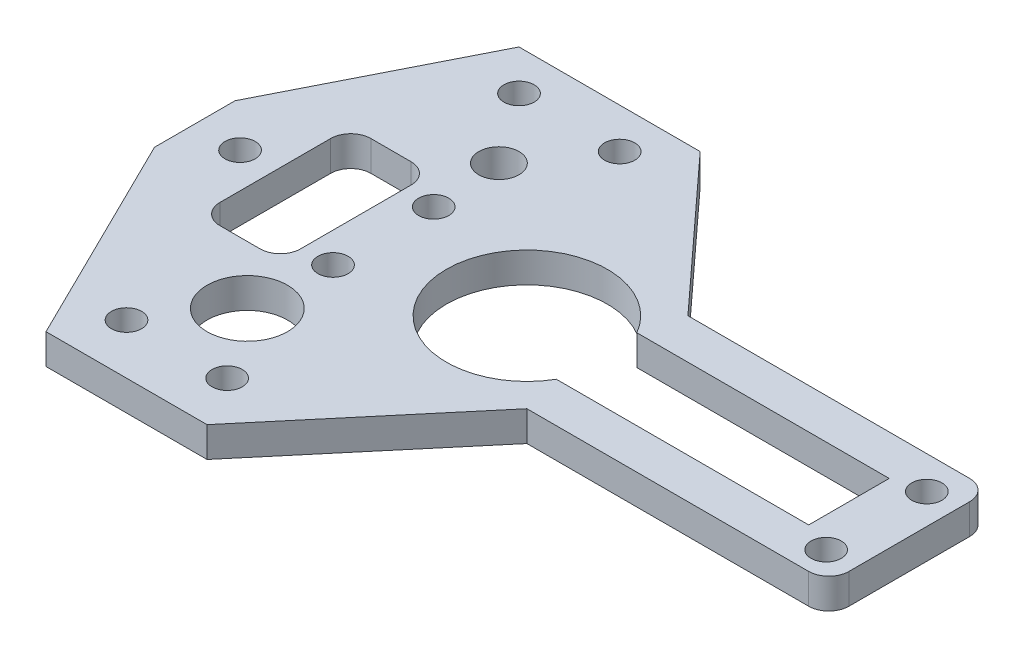
SolidWorks part; units mm, degrees
ref_plane "Piano frontale" through (0, 0, 0) normal (0, 0, 1) x (1, 0, 0)
ref_plane "Piano superiore" through (0, 0, 0) normal (0, 1, 0) x (1, 0, 0)
ref_plane "Piano destro" through (0, 0, 0) normal (1, 0, 0) x (0, 0, -1)
sketch "Sketch1" plane through (0, 0, 0) normal (0, 1, 0) x (1, 0, 0)
  line L0 (-18.4803, -4) -> (-18.4803, 4)
  line L1 (-18.4803, 4) -> (-9, 22.7383)
  line L2 (-9, 22.7383) -> (9, 22.7383)
  line L3 (9, 22.7383) -> (22.5197, 8)
  line L4 (22.5197, 8) -> (52.5197, 8)
  line L5 (52.5197, 8) -> (52.5197, -8)
  line L6 (52.5197, -8) -> (22.5197, -8)
  line L7 (22.5197, -8) -> (8, -25.2617)
  line L8 (8, -25.2617) -> (-8, -25.2617)
  line L9 (-8, -25.2617) -> (-18.4803, -4)
  line L10 (-18.4803, 0) -> (52.5197, 0) construction
  line L11 (0, -25.2617) -> (0, 22.7383) construction
  dimension "D1" = 8
  dimension "D2" = 18
  dimension "D3" = 16
  dimension "D4" = 21
  dimension "D5" = 48
  dimension "D6" = 16
  dimension "D7" = 30
  dimension "D8" = 20
  dimension "D9" = 71
base flange "Base-Flange1" sketch "Sketch1" thickness 3 reverse thickness direction yes parameters "D1"=0.7366
sketch "Sketch2" plane through (0, 3, 0) normal (0, 1, 0) x (1, 0, 0)
  line L0 (-18.4803, 0) -> (52.5197, 0) construction
  line L1 (52.5197, -8) -> (52.5197, 8) construction
  line L3 (21.4479, 4) -> (46.5197, 4)
  line L5 (21.4479, -4) -> (46.5197, -4)
  line L6 (46.5197, 4) -> (46.5197, -4)
  arc A0 (21.4479, 4) -> (21.4479, -4) centre (14.5197, 0) ccw
  point P10 (46.5197, 0)
  dimension "D1" = 16
  dimension "D2" = 38
  dimension "D3" = 8
  dimension "D4" = 6
extrude "Cut-Extrude1" cut sketch "Sketch2" against normal up to next normal cut yes
sketch "Sketch3" plane through (0, 3, 0) normal (0, 1, 0) x (1, 0, 0)
  line L0 (-18.4803, 0) -> (52.5197, 0) construction
  line L1 (-10.4803, -7.5) -> (-2.4803, -7.5)
  line L2 (-10.4803, -7.5) -> (-10.4803, 7.5)
  line L3 (-10.4803, 7.5) -> (-2.4803, 7.5)
  line L4 (-2.4803, -7.5) -> (-2.4803, 7.5)
  line L5 (-10.4803, -7.5) -> (-2.4803, 7.5) construction
  line L6 (-10.4803, 7.5) -> (-2.4803, -7.5) construction
  line L7 (-18.4803, 4) -> (-18.4803, -4) construction
  circle A0 centre (-13.9803, 0) radius 1.5
  arc A1 (21.4479, 4) -> (21.4479, -4) centre (14.5197, 0) ccw construction
  point P0 (-6.4803, 0)
  dimension "D1" = 3
  dimension "D2" = 8
  dimension "D3" = 15
  dimension "D4" = 17
  dimension "D5" = 4.5
extrude "Cut-Extrude2" cut sketch "Sketch3" against normal up to next normal cut yes
sketch "Sketch4" plane through (0, 3, 0) normal (0, 1, 0) x (1, 0, 0)
  line L0 (9, 22.7383) -> (-9, 22.7383) construction
  line L1 (-18.4803, 4) -> (-18.4803, -4) construction
  circle A0 centre (-5, 18.7383) radius 1.5
  circle A1 centre (5, 18.7383) radius 1.5
  circle A2 centre (0.5197, 4.7383) radius 1.5
  circle A3 centre (-5, -20.2617) radius 1.5
  circle A4 centre (5, -20.2617) radius 1.5
  circle A5 centre (0.5197, -5.2617) radius 1.5
  circle A6 centre (49.5197, 4.7383) radius 1.5
  circle A7 centre (49.5197, -5.2617) radius 1.5
  point P11 (0, 22.7383)
  dimension "D1" = 10
  dimension "D2" = 3
  dimension "D5" = 18
  dimension "D3" = 5
  dimension "D4" = 4
  dimension "D6" = 19
  dimension "D7" = 39
  dimension "D8" = 10
  dimension "D9" = 49
extrude "Cut-Extrude3" cut sketch "Sketch4" against normal up to next normal cut yes
sketch "Sketch5" plane through (0, 3, 0) normal (0, 1, 0) x (1, 0, 0)
  line L0 (0, -25.2617) -> (0, 22.7383) construction
  line L1 (-8, -25.2617) -> (8, -25.2617) construction
  line L2 (9, 22.7383) -> (-9, 22.7383) construction
  circle A0 centre (0, 11.7383) radius 2
  circle A1 centre (0, -13.2617) radius 4
  dimension "D1" = 8
  dimension "D4" = 4
  dimension "D2" = 12
  dimension "D3" = 11
extrude "Cut-Extrude4" cut sketch "Sketch5" against normal up to next normal cut yes
fillet "Fillet1" radius 2 6 edges at (-2.4803, 1.5, 7.5) (-10.4803, 1.5, 7.5) (-2.4803, 1.5, -7.5) (-10.4803, 1.5, -7.5) (52.5197, 1.5, 8) (52.5197, 1.5, -8)
sketch "Linee di piegatura1" [suppressed] plane through (0, 0, 0) normal (0, 1, 0) x (1, 0, 0)
sketch "Casella di contorno1" [suppressed] plane through (0, 0, 0) normal (0, 1, 0) x (1, 0, 0)
sheet metal parameters "Lamiera1" thickness 3 parameters "D1"=0.7366
flat pattern "Ripetizione piatta1" [suppressed]
sketch "Linee di piegatura2" plane through (0, 0, 0) normal (0, 1, 0) x (1, 0, 0)
sketch3d "Casella di contorno2" [suppressed]
  line L0 (-53.2984, 24, 0) -> (17.7016, 24, 0) construction
  line L1 (-53.2984, -24, 0) -> (17.7016, -24, 0) construction
  line L2 (-53.2984, 24, 0) -> (-53.2984, -24, 0) construction
  line L3 (17.7016, 24, 0) -> (17.7016, -24, 0) construction
sheet metal parameters "Lamiera2" thickness 3 parameters "D1"=0.7366
flat pattern "Ripetizione piatta1" [suppressed]
sketch "Linee di piegatura2" plane through (0, 0, 0) normal (0, 1, 0) x (1, 0, 0)
sketch3d "Casella di contorno2" [suppressed]
  line L0 (-51, -24, 0) -> (20, -24, 0) construction
  line L1 (-51, 24, 0) -> (20, 24, 0) construction
  line L2 (-51, -24, 0) -> (-51, 24, 0) construction
  line L3 (20, -24, 0) -> (20, 24, 0) construction
sketch "Sketch10-2" [suppressed] plane through (0, 3, 0) normal (0, 1, 0) x (1, 0, 0)
  line L1 (-9, -24) -> (9, -24) construction
  circle A0 centre (0.5197, 10.4281) radius 2
  circle A1 centre (0, -12) radius 4
  dimension "D1" = 4
  dimension "D2" = 8
  dimension "D3" = 12
sheet metal parameters "Lamiera3" thickness 3 parameters "D1"=0.7366
flat pattern "Ripetizione piatta1" [suppressed]
sketch "Linee di piegatura2" plane through (0, 0, 0) normal (0, 1, 0) x (1, 0, 0)
sketch3d "Casella di contorno2" [suppressed]
  line L0 (-51, -24, 0) -> (20, -24, 0) construction
  line L1 (-51, 24, 0) -> (20, 24, 0) construction
  line L2 (-51, -24, 0) -> (-51, 24, 0) construction
  line L3 (20, -24, 0) -> (20, 24, 0) construction
sketch "Sketch10-3" [suppressed] plane through (0, 3, 0) normal (0, 1, 0) x (1, 0, 0)
  line L1 (-9, -24) -> (9, -24) construction
  circle A0 centre (0.5197, 10.4281) radius 2
  circle A1 centre (0, -12) radius 4
  dimension "D1" = 4
  dimension "D2" = 8
  dimension "D3" = 12
sheet metal parameters "Lamiera4" thickness 3 parameters "D1"=0.7366
flat pattern "Ripetizione piatta1" [suppressed]
sketch "Linee di piegatura2" plane through (0, 0, 0) normal (0, 1, 0) x (1, 0, 0)
sketch3d "Casella di contorno2" [suppressed]
  line L0 (-52.5197, -25.2617, 0) -> (18.4803, -25.2617, 0) construction
  line L1 (-52.5197, 22.7383, 0) -> (18.4803, 22.7383, 0) construction
  line L2 (-52.5197, -25.2617, 0) -> (-52.5197, 22.7383, 0) construction
  line L3 (18.4803, -25.2617, 0) -> (18.4803, 22.7383, 0) construction
sketch "Sketch11-1" [suppressed] plane through (0, 3, 0) normal (0, 1, 0) x (1, 0, 0)
sheet metal parameters "Lamiera6" thickness 3 parameters "D1"=0.7366
flat pattern "Ripetizione piatta1"
sketch "Linee di piegatura2" plane through (0, 0, 0) normal (0, 1, 0) x (1, 0, 0)
sketch3d "Casella di contorno2" [suppressed]
  line L0 (-52.5197, -25.2617, 0) -> (18.4803, -25.2617, 0) construction
  line L1 (-52.5197, 22.7383, 0) -> (18.4803, 22.7383, 0) construction
  line L2 (-52.5197, -25.2617, 0) -> (-52.5197, 22.7383, 0) construction
  line L3 (18.4803, -25.2617, 0) -> (18.4803, 22.7383, 0) construction
